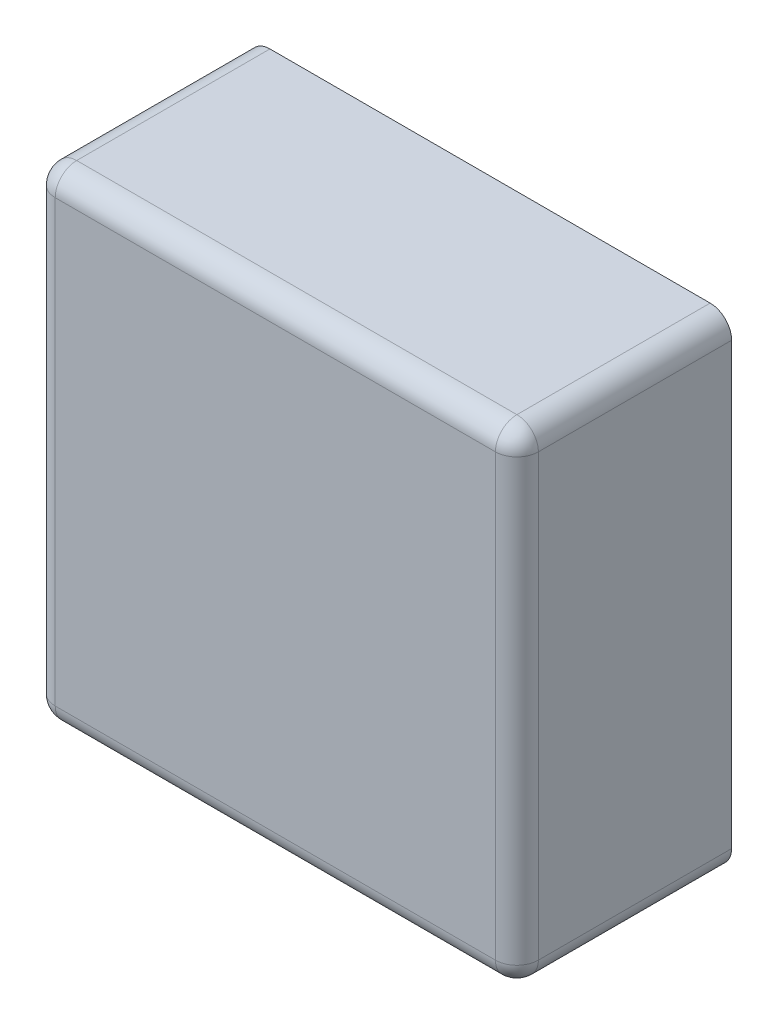
SolidWorks part; units mm, degrees
ref_plane "Piano frontale" through (0, 0, 0) normal (0, 0, 1) x (1, 0, 0)
ref_plane "Piano superiore" through (0, 0, 0) normal (0, 1, 0) x (1, 0, 0)
ref_plane "Piano destro" through (0, 0, 0) normal (1, 0, 0) x (0, 0, -1)
sketch "Schizzo1" plane through (0, 0, 0) normal (0, 0, 1) x (1, 0, 0)
  line L1 (0, 0) -> (45, 0)
  line L2 (0, 0) -> (0, 45)
  line L3 (0, 45) -> (45, 45)
  line L4 (45, 0) -> (45, 45)
  dimension "D1" = 45
  dimension "D2" = 45
  dimension "D3" = 45
  dimension "D4" = 45
extrude "Estrusione-Estrusione1" add sketch "Schizzo1" along normal blind 20
shell "Svuota2" thickness 2 removed face at (22.5, 22.5, 0)
sketch "Schizzo3" plane through (0, 0, 0) normal (0, -1, 0) x (-1, 0, 0)
  line L1 (-34.6883, -17.9455) -> (-41.1883, -17.9455)
  line L2 (-34.6883, -17.9455) -> (-34.6883, -14.1455)
  line L3 (-34.6883, -14.1455) -> (-41.1883, -14.1455)
  line L4 (-41.1883, -17.9455) -> (-41.1883, -14.1455)
  dimension "D1" = 6.5
  dimension "D2" = 3.8
extrude "Taglio-Estrusione1" cut sketch "Schizzo3" against normal blind 2
sketch "Schizzo4" plane through (0, 0, 0) normal (0, -1, 0) x (1, 0, 0)
  line L1 (6.117, 16.4219) -> (23.5848, 16.4219)
  line L2 (6.117, 16.4219) -> (6.117, 10.7114)
  line L3 (6.117, 10.7114) -> (23.5848, 10.7114)
  line L4 (23.5848, 16.4219) -> (23.5848, 10.7114)
extrude "Taglio-Estrusione2" cut sketch "Schizzo4" against normal blind 3
sketch "Schizzo8" plane through (0, 0, 0) normal (0, -1, 0) x (1, 0, 0)
  line L1 (27.8183, 7.521) -> (38.3183, 7.521)
  line L2 (27.8183, 7.521) -> (27.8183, 5.521)
  line L3 (27.8183, 5.521) -> (38.3183, 5.521)
  line L4 (38.3183, 7.521) -> (38.3183, 5.521)
  dimension "D1" = 10.5
  dimension "D2" = 2
extrude "Taglio-Estrusione3" cut sketch "Schizzo8" against normal blind 3
fillet "Raccordo3" radius 2 7 edges at (22.5, 0, 20) (45, 22.5, 20) (0, 0, 10) (0, 22.5, 20) (45, 45, 10) (22.5, 45, 20) (0, 45, 10) tangent propagation no
fillet "Raccordo4" radius 2 2 edges at (44.4142, 0.5858, 19.4142) (45, 0, 9)
